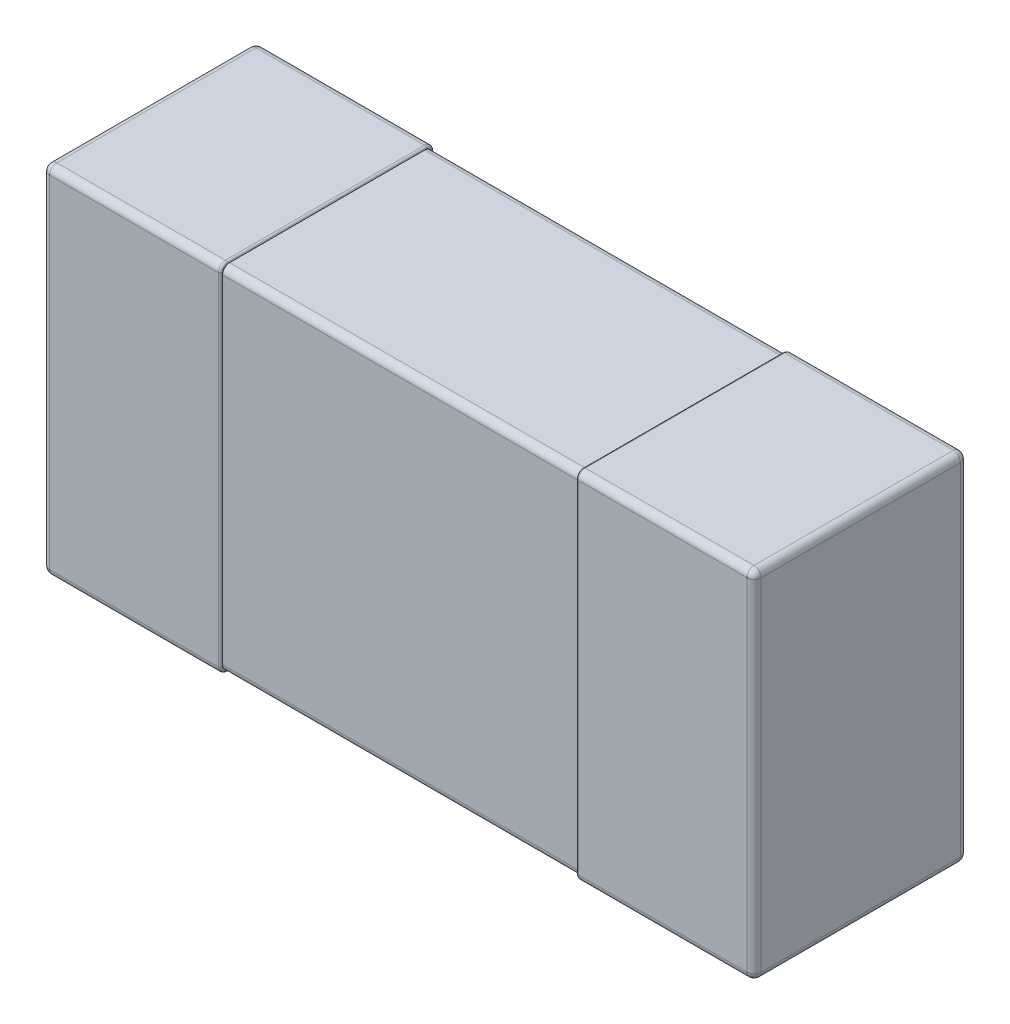
SolidWorks part; units mm, degrees
ref_plane "Top Plane" through (0, 0, 0) normal (0, 0, 1) x (1, 0, 0)
ref_plane "Front Plane" through (0, 0, 0) normal (0, 1, 0) x (1, 0, 0)
ref_plane "Side Plane" through (0, 0, 0) normal (1, 0, 0) x (0, 0, -1)
sketch "Sketch1" plane through (0, 0, 0) normal (0, 0, 1) x (1, 0, 0)
  line L1 (-0.5, 0.25) -> (0.5, 0.25)
  line L2 (-0.5, 0.25) -> (-0.5, -0.25)
  line L3 (-0.5, -0.25) -> (0.5, -0.25)
  line L4 (0.5, 0.25) -> (0.5, -0.25)
  dimension "D1" = 1
  dimension "D2" = 0.5
  dimension "D3" = 0.5
  dimension "D4" = 0.25
extrude "All body" add sketch "Sketch1" along normal blind 0.3
sketch "Sketch2" plane through (0, 0, 0) normal (1, 0, 0) x (0, 0, -1)
  line L14 (-0.003, 0.247) -> (-0.297, 0.247)
  line L15 (-0.003, -0.247) -> (-0.003, 0.247)
  line L16 (-0.297, -0.247) -> (-0.003, -0.247)
  line L17 (-0.297, 0.247) -> (-0.297, -0.247)
  line L18 (-0.003, 0.247) -> (-0.297, 0.247)
  line L19 (-0.003, -0.247) -> (-0.003, 0.247)
  line L20 (-0.297, -0.247) -> (-0.003, -0.247)
  line L21 (-0.297, 0.247) -> (-0.297, -0.247)
  dimension "D1" = 0.003
extrude "Cut out the body for pin" cut sketch "Sketch2" against normal blind 0.25 and the other way blind 0.25 flip side to cut
fillet "Body fillet" radius 0.01 4 edges at (0, 0.247, 0.003) (0, 0.247, 0.297) (0, -0.247, 0.003) (0, -0.247, 0.297)
fillet "Pin fillet a" radius 0.01 16 edges at (0.5, -0.25, 0.15) (0.5, 0, 0.3) (0.5, 0.25, 0.15) (0.5, 0, 0) (-0.5, 0.25, 0.15) (-0.5, 0, 0.3) (-0.5, -0.25, 0.15) (-0.5, 0, 0) (0.375, 0.25, 0.3) (0.375, -0.25, 0.3) (0.375, -0.25, 0) (0.375, 0.25, 0) (-0.375, 0.25, 0) (-0.375, -0.25, 0) (-0.375, 0.25, 0.3) (-0.375, -0.25, 0.3)
fillet "Pin fillet b" radius 0.003 16 edges at (0.25, -0.2471, 0.2971) (0.25, -0.25, 0.15) (0.25, -0.2471, 0.0029) (0.25, 0, 0) (0.25, 0.2471, 0.0029) (0.25, 0.25, 0.15) (0.25, 0.2471, 0.2971) (-0.25, -0.2471, 0.2971) (-0.25, -0.25, 0.15) (-0.25, -0.2471, 0.0029) (-0.25, 0, 0) (-0.25, 0.2471, 0.0029) (-0.25, 0.25, 0.15) (-0.25, 0.2471, 0.2971) (0.25, 0, 0.3) (-0.25, 0, 0.3)
